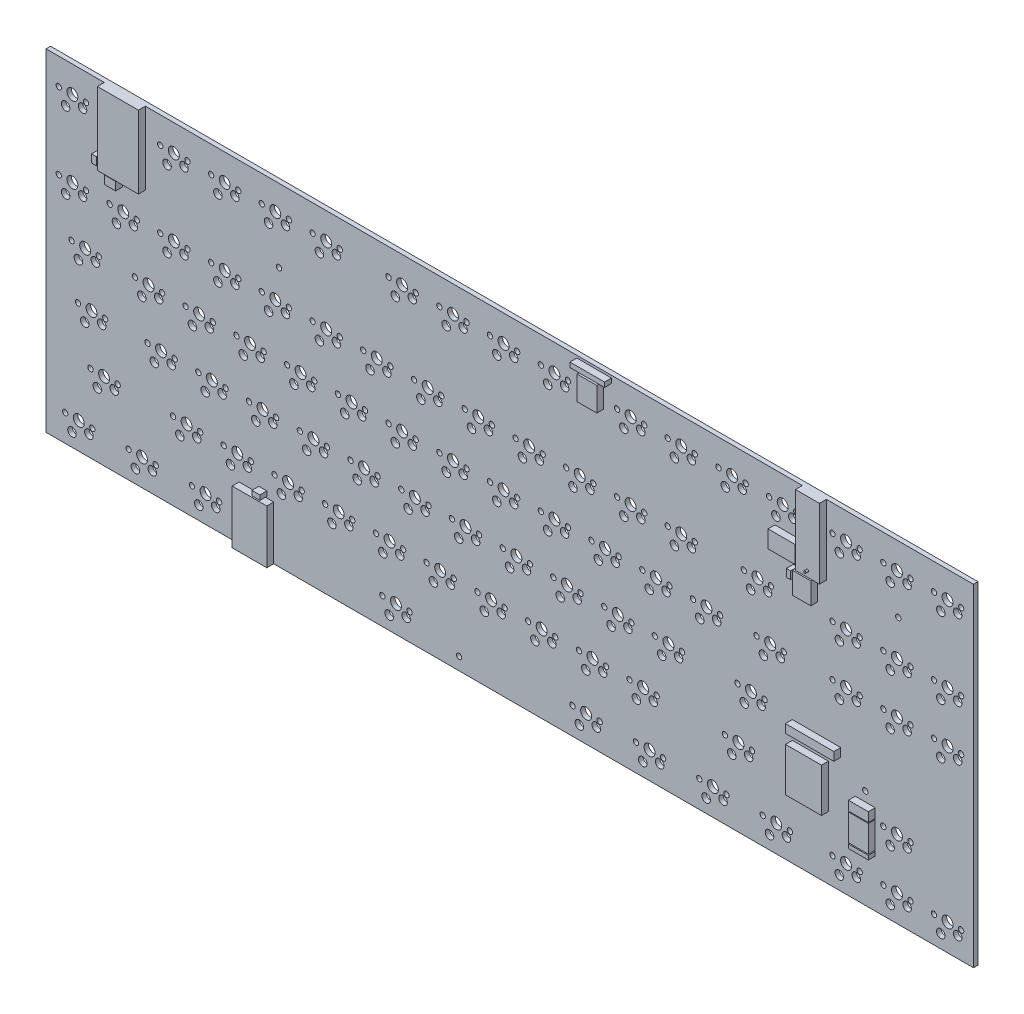
SolidWorks part; units mm, degrees
ref_plane "前视基准面" through (0, 0, 0) normal (0, 0, 1) x (1, 0, 0)
ref_plane "上视基准面" through (0, 0, 0) normal (0, 1, 0) x (1, 0, 0)
ref_plane "右视基准面" through (0, 0, 0) normal (1, 0, 0) x (0, 0, -1)
other "Configuration Table"
sketch "草图1" plane through (0, 0, 0) normal (0, 0, 1) x (1, 0, 0)
  line L9 (0, 0) -> (348.235, 0)
  line L10 (0, 0) -> (0, -124.714)
  line L16 (0, -124.714) -> (348.235, -124.714)
  line L17 (348.235, 0) -> (348.235, -124.714)
  dimension "D2" = 348.235
  dimension "D1" = 124.714
extrude "凸台-拉伸1" add sketch "草图1" along normal blind 1.7
sketch "草图3" plane through (0, 0, 1.7) normal (0, 0, 1) x (1, 0, 0)
  line L0 (0, 0) -> (0, -124.714) construction
  line L1 (348.235, 0) -> (0, 0) construction
  circle A0 centre (87.5, -27.4) radius 1
  circle A1 centre (155.1, -120) radius 1
  circle A2 centre (307.6, -87.5) radius 1
  circle A3 centre (320, -24.9) radius 1
  dimension "D1" = 2
  dimension "D2" = 87.5
  dimension "D3" = 27.4
  dimension "D4" = 155.1
  dimension "D5" = 120
  dimension "D6" = 307.6
  dimension "D7" = 87.5
  dimension "D8" = 320
  dimension "D9" = 24.9
extrude "切除-拉伸1" cut sketch "草图3" against normal through all
sketch "草图4" plane through (0, 0, 1.7) normal (0, 0, 1) x (1, 0, 0)
  line L0 (0, 0) -> (0, -124.714) construction
  line L1 (348.235, 0) -> (0, 0) construction
  circle A0 centre (9.9, -9.9) radius 2.05
  circle A1 centre (7.36, -14.91) radius 1.6
  circle A2 centre (13.71, -12.44) radius 1.6
  circle A3 centre (9.9, -38.5) radius 2.05
  circle A4 centre (7.36, -43.51) radius 1.6
  circle A5 centre (13.71, -41.04) radius 1.6
  circle A6 centre (14.7, -57.5) radius 2.05
  circle A7 centre (12.16, -62.51) radius 1.6
  circle A8 centre (18.51, -60.04) radius 1.6
  circle A9 centre (17.1, -76.6) radius 2.05
  circle A10 centre (14.56, -81.61) radius 1.6
  circle A11 centre (20.91, -79.14) radius 1.6
  circle A12 centre (21.8, -95.6) radius 2.05
  circle A13 centre (19.26, -100.61) radius 1.6
  circle A14 centre (25.61, -98.14) radius 1.6
  circle A15 centre (12.3, -114.7) radius 2.05
  circle A16 centre (9.76, -119.71) radius 1.6
  circle A17 centre (16.11, -117.24) radius 1.6
  circle A18 centre (48, -9.9) radius 2.05
  circle A19 centre (45.46, -14.91) radius 1.6
  circle A20 centre (51.81, -12.44) radius 1.6
  circle A21 centre (105.2, -9.9) radius 2.05
  circle A22 centre (102.66, -14.91) radius 1.6
  circle A23 centre (109.01, -12.44) radius 1.6
  circle A24 centre (133.7, -9.9) radius 2.05
  circle A25 centre (131.16, -14.91) radius 1.6
  circle A26 centre (137.51, -12.44) radius 1.6
  circle A27 centre (190.9, -9.9) radius 2.05
  circle A28 centre (188.36, -14.91) radius 1.6
  circle A29 centre (194.71, -12.44) radius 1.6
  circle A30 centre (219.5, -9.9) radius 2.05
  circle A31 centre (216.96, -14.91) radius 1.6
  circle A32 centre (223.31, -12.44) radius 1.6
  circle A33 centre (276.6, -9.9) radius 2.05
  circle A34 centre (274.06, -14.91) radius 1.6
  circle A35 centre (280.41, -12.44) radius 1.6
  circle A36 centre (300.4, -9.9) radius 2.05
  circle A37 centre (297.86, -14.91) radius 1.6
  circle A38 centre (304.21, -12.44) radius 1.6
  circle A39 centre (338.5, -9.9) radius 2.05
  circle A40 centre (335.96, -14.91) radius 1.6
  circle A41 centre (342.31, -12.44) radius 1.6
  circle A42 centre (260, -95.6) radius 2.05
  circle A43 centre (257.46, -100.61) radius 1.6
  circle A44 centre (263.81, -98.14) radius 1.6
  circle A45 centre (264.7, -76.6) radius 2.05
  circle A46 centre (262.16, -81.61) radius 1.6
  circle A47 centre (268.51, -79.14) radius 1.6
  circle A48 centre (271.9, -57.5) radius 2.05
  circle A49 centre (269.36, -62.51) radius 1.6
  circle A50 centre (275.71, -60.04) radius 1.6
  circle A51 centre (267.1, -38.5) radius 2.05
  circle A52 centre (264.56, -43.51) radius 1.6
  circle A53 centre (270.91, -41.04) radius 1.6
  circle A54 centre (274.2, -114.7) radius 2.05
  circle A55 centre (271.66, -119.71) radius 1.6
  circle A56 centre (278.01, -117.24) radius 1.6
  circle A57 centre (300.4, -38.5) radius 2.05
  circle A58 centre (297.86, -43.51) radius 1.6
  circle A59 centre (304.21, -41.04) radius 1.6
  circle A60 centre (338.5, -38.5) radius 2.05
  circle A61 centre (335.96, -43.51) radius 1.6
  circle A62 centre (342.31, -41.04) radius 1.6
  circle A63 centre (300.4, -57.5) radius 2.05
  circle A64 centre (297.86, -62.51) radius 1.6
  circle A65 centre (304.21, -60.04) radius 1.6
  circle A66 centre (338.5, -57.5) radius 2.05
  circle A67 centre (335.96, -62.51) radius 1.6
  circle A68 centre (342.31, -60.04) radius 1.6
  circle A69 centre (300.4, -114.7) radius 2.05
  circle A70 centre (297.86, -119.71) radius 1.6
  circle A71 centre (304.21, -117.24) radius 1.6
  circle A72 centre (319.5, -114.7) radius 2.05
  circle A73 centre (316.96, -119.71) radius 1.6
  circle A74 centre (323.31, -117.24) radius 1.6
  circle A75 centre (338.5, -114.7) radius 2.05
  circle A76 centre (335.96, -119.71) radius 1.6
  circle A77 centre (342.31, -117.24) radius 1.6
  circle A78 centre (319.5, -95.6) radius 2.05
  circle A79 centre (316.96, -100.61) radius 1.6
  circle A80 centre (323.31, -98.14) radius 1.6
  circle A81 centre (319.5, -57.5) radius 2.05
  circle A82 centre (316.96, -62.51) radius 1.6
  circle A83 centre (323.31, -60.04) radius 1.6
  circle A84 centre (319.5, -38.5) radius 2.05
  circle A85 centre (316.96, -43.51) radius 1.6
  circle A86 centre (323.31, -41.04) radius 1.6
  circle A87 centre (319.5, -9.9) radius 2.05
  circle A88 centre (316.96, -14.91) radius 1.6
  circle A89 centre (323.31, -12.44) radius 1.6
  circle A90 centre (131.4, -114.7) radius 2.05
  circle A91 centre (128.86, -119.71) radius 1.6
  circle A92 centre (135.21, -117.24) radius 1.6
  circle A93 centre (67.1, -9.9) radius 2.05
  circle A94 centre (64.56, -14.91) radius 1.6
  circle A95 centre (70.91, -12.44) radius 1.6
  circle A96 centre (86.1, -9.9) radius 2.05
  circle A97 centre (83.56, -14.91) radius 1.6
  circle A98 centre (89.91, -12.44) radius 1.6
  circle A99 centre (152.8, -9.9) radius 2.05
  circle A100 centre (150.26, -14.91) radius 1.6
  circle A101 centre (156.61, -12.44) radius 1.6
  circle A102 centre (171.8, -9.9) radius 2.05
  circle A103 centre (169.26, -14.91) radius 1.6
  circle A104 centre (175.61, -12.44) radius 1.6
  circle A105 centre (238.5, -9.9) radius 2.05
  circle A106 centre (235.96, -14.91) radius 1.6
  circle A107 centre (242.31, -12.44) radius 1.6
  circle A108 centre (257.6, -9.9) radius 2.05
  circle A109 centre (255.06, -14.91) radius 1.6
  circle A110 centre (261.41, -12.44) radius 1.6
  dimension "D1" = 4.1
  dimension "D8" = 3.2
  dimension "D9" = 3.2
  dimension "D10" = 4.1
  dimension "D15" = 3.2
  dimension "D16" = 3.2
  dimension "D19" = 4.1
  dimension "D24" = 3.2
  dimension "D25" = 3.2
  dimension "D28" = 4.1
  dimension "D33" = 3.2
  dimension "D34" = 3.2
  dimension "D37" = 4.1
  dimension "D42" = 3.2
  dimension "D43" = 3.2
  dimension "D46" = 4.1
  dimension "D51" = 3.2
  dimension "D52" = 3.2
  dimension "D55" = 4.1
  dimension "D60" = 3.2
  dimension "D61" = 3.2
  dimension "D63" = 4.1
  dimension "D68" = 3.2
  dimension "D69" = 3.2
  dimension "D75" = 3.2
  dimension "D76" = 3.2
  dimension "D78" = 4.1
  dimension "D83" = 3.2
  dimension "D84" = 3.2
  dimension "D85" = 4.1
  dimension "D91" = 3.2
  dimension "D92" = 3.2
  dimension "D93" = 4.1
  dimension "D98" = 3.2
  dimension "D99" = 3.2
  dimension "D100" = 4.1
  dimension "D105" = 3.2
  dimension "D106" = 3.2
  dimension "D107" = 4.1
  dimension "D112" = 3.2
  dimension "D113" = 3.2
  dimension "D114" = 4.1
  dimension "D123" = 3.2
  dimension "D124" = 4.1
  dimension "D126" = 3.2
  dimension "D131" = 3.2
  dimension "D132" = 4.1
  dimension "D133" = 3.2
  dimension "D138" = 3.2
  dimension "D139" = 4.1
  dimension "D140" = 3.2
  dimension "D145" = 3.2
  dimension "D146" = 4.1
  dimension "D147" = 3.2
  dimension "D152" = 3.2
  dimension "D153" = 4.1
  dimension "D154" = 3.2
  dimension "D163" = 3.2
  dimension "D164" = 4.1
  dimension "D165" = 3.2
  dimension "D170" = 3.2
  dimension "D171" = 4.1
  dimension "D172" = 3.2
  dimension "D177" = 3.2
  dimension "D178" = 4.1
  dimension "D179" = 3.2
  dimension "D184" = 3.2
  dimension "D185" = 4.1
  dimension "D186" = 3.2
  dimension "D191" = 3.2
  dimension "D192" = 4.1
  dimension "D193" = 3.2
  dimension "D198" = 3.2
  dimension "D199" = 4.1
  dimension "D200" = 3.2
  dimension "D205" = 3.2
  dimension "D206" = 4.1
  dimension "D207" = 3.2
  dimension "D212" = 3.2
  dimension "D213" = 4.1
  dimension "D214" = 3.2
  dimension "D219" = 3.2
  dimension "D220" = 4.1
  dimension "D221" = 3.2
  dimension "D226" = 3.2
  dimension "D227" = 4.1
  dimension "D228" = 3.2
  dimension "D233" = 3.2
  dimension "D234" = 4.1
  dimension "D235" = 3.2
  dimension "D241" = 3.2
  dimension "D242" = 4.1
  dimension "D243" = 3.2
  dimension "D245" = 4.1
  dimension "D250" = 3.2
  dimension "D251" = 3.2
  dimension "D252" = 4.1
  dimension "D257" = 3.2
  dimension "D258" = 3.2
  dimension "D259" = 4.1
  dimension "D264" = 3.2
  dimension "D265" = 3.2
  dimension "D266" = 4.1
  dimension "D271" = 3.2
  dimension "D272" = 3.2
  dimension "D273" = 4.1
  dimension "D278" = 3.2
  dimension "D279" = 3.2
  dimension "D280" = 4.1
  dimension "D285" = 3.2
  dimension "D286" = 3.2
  dimension "D2" = 9.9
  dimension "D3" = 9.9
  dimension "D4" = 5.01
  dimension "D5" = 2.54
  dimension "D6" = 3.81
  dimension "D7" = 2.54
  dimension "D11" = 5.01
  dimension "D12" = 2.54
  dimension "D13" = 3.81
  dimension "D14" = 2.54
  dimension "D17" = 9.9
  dimension "D18" = 38.5
  dimension "D20" = 5.01
  dimension "D21" = 2.54
  dimension "D22" = 3.81
  dimension "D23" = 2.54
  dimension "D26" = 14.7
  dimension "D27" = 57.5
  dimension "D29" = 5.01
  dimension "D30" = 2.54
  dimension "D31" = 3.81
  dimension "D32" = 2.54
  dimension "D35" = 17.1
  dimension "D36" = 76.6
  dimension "D38" = 5.01
  dimension "D39" = 2.54
  dimension "D40" = 3.81
  dimension "D41" = 2.54
  dimension "D44" = 21.8
  dimension "D45" = 95.6
  dimension "D47" = 5.01
  dimension "D48" = 2.54
  dimension "D49" = 3.81
  dimension "D50" = 2.54
  dimension "D53" = 12.3
  dimension "D54" = 114.7
  dimension "D56" = 5.01
  dimension "D57" = 2.54
  dimension "D58" = 3.81
  dimension "D59" = 2.54
  dimension "D62" = 48
  dimension "D64" = 5.01
  dimension "D65" = 2.54
  dimension "D66" = 3.81
  dimension "D67" = 2.54
  dimension "D70" = 105.2
  dimension "D71" = 5.01
  dimension "D72" = 2.54
  dimension "D73" = 3.81
  dimension "D74" = 2.54
  dimension "D77" = 133.7
  dimension "D79" = 5.01
  dimension "D80" = 2.54
  dimension "D81" = 3.81
  dimension "D82" = 2.54
  dimension "D86" = 190.9
  dimension "D87" = 5.01
  dimension "D88" = 2.54
  dimension "D89" = 3.81
  dimension "D90" = 2.54
  dimension "D94" = 5.01
  dimension "D95" = 2.54
  dimension "D96" = 3.81
  dimension "D97" = 2.54
  dimension "D101" = 5.01
  dimension "D102" = 2.54
  dimension "D103" = 3.81
  dimension "D104" = 2.54
  dimension "D108" = 5.01
  dimension "D109" = 2.54
  dimension "D110" = 3.81
  dimension "D111" = 2.54
  dimension "D115" = 219.5
  dimension "D116" = 276.6
  dimension "D117" = 300.4
  dimension "D118" = 338.5
  dimension "D119" = 5.01
  dimension "D120" = 2.54
  dimension "D121" = 3.81
  dimension "D122" = 2.54
  dimension "D125" = 260
  dimension "D127" = 5.01
  dimension "D128" = 2.54
  dimension "D129" = 3.81
  dimension "D130" = 2.54
  dimension "D134" = 5.01
  dimension "D135" = 2.54
  dimension "D136" = 3.81
  dimension "D137" = 2.54
  dimension "D141" = 5.01
  dimension "D142" = 2.54
  dimension "D143" = 3.81
  dimension "D144" = 2.54
  dimension "D148" = 5.01
  dimension "D149" = 2.54
  dimension "D150" = 3.81
  dimension "D151" = 2.54
  dimension "D155" = 264.7
  dimension "D156" = 271.9
  dimension "D157" = 267.1
  dimension "D158" = 274.2
  dimension "D159" = 5.01
  dimension "D160" = 2.54
  dimension "D161" = 3.81
  dimension "D162" = 2.54
  dimension "D166" = 5.01
  dimension "D167" = 2.54
  dimension "D168" = 3.81
  dimension "D169" = 2.54
  dimension "D173" = 5.01
  dimension "D174" = 2.54
  dimension "D175" = 3.81
  dimension "D176" = 2.54
  dimension "D180" = 5.01
  dimension "D181" = 2.54
  dimension "D182" = 3.81
  dimension "D183" = 2.54
  dimension "D187" = 5.01
  dimension "D188" = 2.54
  dimension "D189" = 3.81
  dimension "D190" = 2.54
  dimension "D194" = 5.01
  dimension "D195" = 2.54
  dimension "D196" = 3.81
  dimension "D197" = 2.54
  dimension "D201" = 5.01
  dimension "D202" = 2.54
  dimension "D203" = 3.81
  dimension "D204" = 2.54
  dimension "D208" = 5.01
  dimension "D209" = 2.54
  dimension "D210" = 3.81
  dimension "D211" = 2.54
  dimension "D215" = 5.01
  dimension "D216" = 2.54
  dimension "D217" = 3.81
  dimension "D218" = 2.54
  dimension "D222" = 5.01
  dimension "D223" = 2.54
  dimension "D224" = 3.81
  dimension "D225" = 2.54
  dimension "D229" = 5.01
  dimension "D230" = 2.54
  dimension "D231" = 3.81
  dimension "D232" = 2.54
  dimension "D236" = 319.5
  dimension "D237" = 5.01
  dimension "D238" = 2.54
  dimension "D239" = 3.81
  dimension "D240" = 2.54
  dimension "D244" = 131.4
  dimension "D246" = 5.01
  dimension "D247" = 2.54
  dimension "D248" = 3.81
  dimension "D249" = 2.54
  dimension "D253" = 5.01
  dimension "D254" = 2.54
  dimension "D255" = 3.81
  dimension "D256" = 2.54
  dimension "D260" = 5.01
  dimension "D261" = 2.54
  dimension "D262" = 3.81
  dimension "D263" = 2.54
  dimension "D267" = 5.01
  dimension "D268" = 2.54
  dimension "D269" = 3.81
  dimension "D270" = 2.54
  dimension "D274" = 5.01
  dimension "D275" = 2.54
  dimension "D276" = 3.81
  dimension "D277" = 2.54
  dimension "D281" = 5.01
  dimension "D282" = 2.54
  dimension "D283" = 3.81
  dimension "D284" = 2.54
  dimension "D287" = 67.1
  dimension "D288" = 86.1
  dimension "D289" = 152.8
  dimension "D290" = 171.8
  dimension "D291" = 238.5
  dimension "D292" = 257.6
extrude "切除-拉伸2" cut sketch "草图4" against normal through all
sketch "草图5" plane through (0, 0, 1.7) normal (0, 0, 1) x (1, 0, 0)
  line L0 (348.235, 0) -> (0, 0) construction
  line L1 (0, 0) -> (0, -124.714) construction
  line L2 (23.9, -38.5) -> (29, -38.5) construction
  line L3 (42.9, -38.5) -> (48, -38.5) construction
  line L4 (48, -38.5) -> (53.1, -38.5) construction
  line L5 (62, -38.5) -> (67.1, -38.5) construction
  line L6 (67.1, -38.5) -> (72.2, -38.5) construction
  line L7 (81, -38.5) -> (86.1, -38.5) construction
  line L8 (86.1, -38.5) -> (91.2, -38.5) construction
  line L9 (100.1, -38.5) -> (105.2, -38.5) construction
  line L10 (105.2, -38.5) -> (110.3, -38.5) construction
  line L11 (119.1, -38.5) -> (124.2, -38.5) construction
  line L12 (124.2, -38.5) -> (129.3, -38.5) construction
  line L13 (157.2, -38.5) -> (162.3, -38.5) construction
  line L14 (162.3, -38.5) -> (167.4, -38.5) construction
  line L15 (138.2, -38.5) -> (143.3, -38.5) construction
  line L16 (143.3, -38.5) -> (148.4, -38.5) construction
  line L17 (176.3, -38.5) -> (181.4, -38.5) construction
  line L18 (181.4, -38.5) -> (186.5, -38.5) construction
  line L19 (195.3, -38.5) -> (200.4, -38.5) construction
  line L20 (200.4, -38.5) -> (205.5, -38.5) construction
  line L21 (214.4, -38.5) -> (219.5, -38.5) construction
  line L22 (219.5, -38.5) -> (224.6, -38.5) construction
  line L23 (233.4, -38.5) -> (238.5, -38.5) construction
  line L24 (238.5, -38.5) -> (243.6, -38.5) construction
  line L25 (29, -38.5) -> (34.1, -38.5) construction
  circle A0 centre (29, -38.5) radius 2.05
  circle A1 centre (26.46, -43.51) radius 1.6
  circle A2 centre (32.81, -41.04) radius 1.6
  circle A3 centre (48, -38.5) radius 2.05
  circle A4 centre (45.46, -43.51) radius 1.6
  circle A5 centre (51.81, -41.04) radius 1.6
  circle A6 centre (67.1, -38.5) radius 2.05
  circle A7 centre (64.56, -43.51) radius 1.6
  circle A8 centre (70.91, -41.04) radius 1.6
  circle A9 centre (86.1, -38.5) radius 2.05
  circle A10 centre (83.56, -43.51) radius 1.6
  circle A11 centre (89.91, -41.04) radius 1.6
  circle A12 centre (105.2, -38.5) radius 2.05
  circle A13 centre (102.66, -43.51) radius 1.6
  circle A14 centre (109.01, -41.04) radius 1.6
  circle A15 centre (124.2, -38.5) radius 2.05
  circle A16 centre (121.66, -43.51) radius 1.6
  circle A17 centre (128.01, -41.04) radius 1.6
  circle A19 centre (143.3, -38.5) radius 2.05
  circle A20 centre (140.76, -43.51) radius 1.6
  circle A21 centre (147.11, -41.04) radius 1.6
  circle A22 centre (162.3, -38.5) radius 2.05
  circle A23 centre (159.76, -43.51) radius 1.6
  circle A24 centre (166.11, -41.04) radius 1.6
  circle A25 centre (181.4, -38.5) radius 2.05
  circle A26 centre (178.86, -43.51) radius 1.6
  circle A27 centre (185.21, -41.04) radius 1.6
  circle A28 centre (200.4, -38.5) radius 2.05
  circle A29 centre (197.86, -43.51) radius 1.6
  circle A30 centre (204.21, -41.04) radius 1.6
  circle A31 centre (219.5, -38.5) radius 2.05
  circle A32 centre (216.96, -43.51) radius 1.6
  circle A33 centre (223.31, -41.04) radius 1.6
  circle A34 centre (238.5, -38.5) radius 2.05
  circle A35 centre (235.96, -43.51) radius 1.6
  circle A36 centre (242.31, -41.04) radius 1.6
  circle A37 centre (23.9, -38.5) radius 1
  circle A38 centre (34.1, -38.5) radius 1
  circle A39 centre (42.9, -38.5) radius 1
  circle A40 centre (53.1, -38.5) radius 1
  circle A41 centre (62, -38.5) radius 1
  circle A42 centre (72.2, -38.5) radius 1
  circle A43 centre (81, -38.5) radius 1
  circle A44 centre (91.2, -38.5) radius 1
  circle A45 centre (100.1, -38.5) radius 1
  circle A46 centre (110.3, -38.5) radius 1
  circle A47 centre (119.1, -38.5) radius 1
  circle A48 centre (129.3, -38.5) radius 1
  circle A49 centre (138.2, -38.5) radius 1
  circle A50 centre (148.4, -38.5) radius 1
  circle A51 centre (157.2, -38.5) radius 1
  circle A52 centre (167.4, -38.5) radius 1
  circle A53 centre (176.3, -38.5) radius 1
  circle A54 centre (186.5, -38.5) radius 1
  circle A55 centre (195.3, -38.5) radius 1
  circle A56 centre (205.5, -38.5) radius 1
  circle A57 centre (214.4, -38.5) radius 1
  circle A58 centre (224.6, -38.5) radius 1
  circle A59 centre (233.4, -38.5) radius 1
  circle A60 centre (243.6, -38.5) radius 1
  dimension "D1" = 4.1
  dimension "D6" = 3.2
  dimension "D7" = 3.2
  dimension "D8" = 4.1
  dimension "D13" = 3.2
  dimension "D14" = 3.2
  dimension "D15" = 4.1
  dimension "D20" = 3.2
  dimension "D21" = 3.2
  dimension "D22" = 4.1
  dimension "D27" = 3.2
  dimension "D28" = 3.2
  dimension "D29" = 4.1
  dimension "D34" = 3.2
  dimension "D35" = 3.2
  dimension "D36" = 4.1
  dimension "D41" = 3.2
  dimension "D42" = 3.2
  dimension "D50" = 4.1
  dimension "D55" = 3.2
  dimension "D56" = 3.2
  dimension "D57" = 4.1
  dimension "D62" = 3.2
  dimension "D63" = 3.2
  dimension "D64" = 4.1
  dimension "D69" = 3.2
  dimension "D70" = 3.2
  dimension "D71" = 4.1
  dimension "D76" = 3.2
  dimension "D77" = 3.2
  dimension "D78" = 4.1
  dimension "D83" = 3.2
  dimension "D84" = 3.2
  dimension "D85" = 4.1
  dimension "D90" = 3.2
  dimension "D91" = 3.2
  dimension "D98" = 2
  dimension "D2" = 5.01
  dimension "D3" = 2.54
  dimension "D4" = 3.81
  dimension "D5" = 2.54
  dimension "D9" = 5.01
  dimension "D10" = 2.54
  dimension "D11" = 3.81
  dimension "D12" = 2.54
  dimension "D16" = 5.01
  dimension "D17" = 2.54
  dimension "D18" = 3.81
  dimension "D19" = 2.54
  dimension "D23" = 5.01
  dimension "D24" = 2.54
  dimension "D25" = 3.81
  dimension "D26" = 2.54
  dimension "D30" = 5.01
  dimension "D31" = 2.54
  dimension "D32" = 3.81
  dimension "D33" = 2.54
  dimension "D37" = 5.01
  dimension "D38" = 2.54
  dimension "D39" = 3.81
  dimension "D40" = 2.54
  dimension "D43" = 38.5
  dimension "D44" = 29
  dimension "D45" = 48
  dimension "D46" = 67.1
  dimension "D47" = 86.1
  dimension "D48" = 105.2
  dimension "D49" = 124.2
  dimension "D51" = 5.01
  dimension "D52" = 2.54
  dimension "D53" = 3.81
  dimension "D54" = 2.54
  dimension "D58" = 5.01
  dimension "D59" = 2.54
  dimension "D60" = 3.81
  dimension "D61" = 2.54
  dimension "D65" = 5.01
  dimension "D66" = 2.54
  dimension "D67" = 3.81
  dimension "D68" = 2.54
  dimension "D72" = 5.01
  dimension "D73" = 2.54
  dimension "D74" = 3.81
  dimension "D75" = 2.54
  dimension "D79" = 5.01
  dimension "D80" = 2.54
  dimension "D81" = 3.81
  dimension "D82" = 2.54
  dimension "D86" = 5.01
  dimension "D87" = 2.54
  dimension "D88" = 3.81
  dimension "D89" = 2.54
  dimension "D92" = 143.3
  dimension "D93" = 162.3
  dimension "D94" = 181.4
  dimension "D95" = 200.4
  dimension "D96" = 219.5
  dimension "D97" = 238.5
  dimension "D99" = 5.1
extrude "切除-拉伸3" cut sketch "草图5" against normal through all
sketch "草图6" plane through (0, 0, 1.7) normal (0, 0, 1) x (1, 0, 0)
  line L0 (348.235, 0) -> (0, 0) construction
  line L1 (0, 0) -> (0, -124.714) construction
  circle A0 centre (38.5, -57.5) radius 2.05
  circle A1 centre (35.96, -62.51) radius 1.6
  circle A2 centre (42.31, -60.04) radius 1.6
  circle A34 centre (33.4, -57.5) radius 1
  circle A35 centre (43.6, -57.5) radius 1
  circle A36 centre (57.5, -57.5) radius 2.05
  circle A37 centre (54.96, -62.51) radius 1.6
  circle A38 centre (61.31, -60.04) radius 1.6
  circle A39 centre (52.4, -57.5) radius 1
  circle A40 centre (62.6, -57.5) radius 1
  circle A41 centre (76.6, -57.5) radius 2.05
  circle A42 centre (74.06, -62.51) radius 1.6
  circle A43 centre (80.41, -60.04) radius 1.6
  circle A44 centre (71.5, -57.5) radius 1
  circle A45 centre (81.7, -57.5) radius 1
  circle A46 centre (95.6, -57.5) radius 2.05
  circle A47 centre (93.06, -62.51) radius 1.6
  circle A48 centre (99.41, -60.04) radius 1.6
  circle A49 centre (90.5, -57.5) radius 1
  circle A50 centre (100.7, -57.5) radius 1
  circle A51 centre (114.7, -57.5) radius 2.05
  circle A52 centre (112.16, -62.51) radius 1.6
  circle A53 centre (118.51, -60.04) radius 1.6
  circle A54 centre (109.6, -57.5) radius 1
  circle A55 centre (119.8, -57.5) radius 1
  circle A56 centre (133.7, -57.5) radius 2.05
  circle A57 centre (131.16, -62.51) radius 1.6
  circle A58 centre (137.51, -60.04) radius 1.6
  circle A59 centre (128.6, -57.5) radius 1
  circle A60 centre (138.8, -57.5) radius 1
  circle A61 centre (152.8, -57.5) radius 2.05
  circle A62 centre (150.26, -62.51) radius 1.6
  circle A63 centre (156.61, -60.04) radius 1.6
  circle A64 centre (147.7, -57.5) radius 1
  circle A65 centre (157.9, -57.5) radius 1
  circle A66 centre (171.8, -57.5) radius 2.05
  circle A67 centre (169.26, -62.51) radius 1.6
  circle A68 centre (175.61, -60.04) radius 1.6
  circle A69 centre (166.7, -57.5) radius 1
  circle A70 centre (176.9, -57.5) radius 1
  circle A71 centre (190.9, -57.5) radius 2.05
  circle A72 centre (188.36, -62.51) radius 1.6
  circle A73 centre (194.71, -60.04) radius 1.6
  circle A74 centre (185.8, -57.5) radius 1
  circle A75 centre (196, -57.5) radius 1
  circle A76 centre (209.9, -57.5) radius 2.05
  circle A77 centre (207.36, -62.51) radius 1.6
  circle A78 centre (213.71, -60.04) radius 1.6
  circle A79 centre (204.8, -57.5) radius 1
  circle A80 centre (215, -57.5) radius 1
  circle A81 centre (229, -57.5) radius 2.05
  circle A82 centre (226.46, -62.51) radius 1.6
  circle A83 centre (232.81, -60.04) radius 1.6
  circle A84 centre (223.9, -57.5) radius 1
  circle A85 centre (234.1, -57.5) radius 1
  circle A86 centre (248, -57.5) radius 2.05
  circle A87 centre (245.46, -62.51) radius 1.6
  circle A88 centre (251.81, -60.04) radius 1.6
  circle A89 centre (242.9, -57.5) radius 1
  circle A90 centre (253.1, -57.5) radius 1
  dimension "D1" = 4.1
  dimension "D6" = 3.2
  dimension "D7" = 3.2
  dimension "D8" = 5.1
  dimension "D13" = 2.54
  dimension "D14" = 3.81
  dimension "D15" = 2.54
  dimension "D20" = 2
  dimension "D21" = 4.1
  dimension "D22" = 5.01
  dimension "D27" = 3.2
  dimension "D28" = 5.1
  dimension "D29" = 5.1
  dimension "D34" = 3.81
  dimension "D35" = 2.54
  dimension "D36" = 3.2
  dimension "D41" = 4.1
  dimension "D42" = 5.01
  dimension "D43" = 2.54
  dimension "D48" = 5.1
  dimension "D49" = 5.1
  dimension "D50" = 2
  dimension "D55" = 2.54
  dimension "D56" = 3.2
  dimension "D57" = 3.2
  dimension "D62" = 5.01
  dimension "D63" = 2.54
  dimension "D64" = 3.81
  dimension "D69" = 5.1
  dimension "D70" = 2
  dimension "D71" = 4.1
  dimension "D76" = 3.2
  dimension "D77" = 3.2
  dimension "D10" = 2
  dimension "D11" = 4.1
  dimension "D16" = 3.2
  dimension "D17" = 3.2
  dimension "D26" = 3.2
  dimension "D30" = 2
  dimension "D31" = 4.1
  dimension "D37" = 3.2
  dimension "D40" = 2
  dimension "D46" = 3.2
  dimension "D47" = 3.2
  dimension "D51" = 4.1
  dimension "D60" = 2
  dimension "D61" = 4.1
  dimension "D66" = 3.2
  dimension "D67" = 3.2
  dimension "D81" = 2
  dimension "D82" = 4.1
  dimension "D87" = 3.2
  dimension "D88" = 3.2
  dimension "D91" = 2
  dimension "D92" = 4.1
  dimension "D97" = 3.2
  dimension "D98" = 3.2
  dimension "D101" = 2
  dimension "D102" = 4.1
  dimension "D107" = 3.2
  dimension "D108" = 3.2
  dimension "D111" = 2
  dimension "D123" = 4.1
  dimension "D128" = 3.2
  dimension "D129" = 3.2
  dimension "D132" = 2
  dimension "D2" = 5.01
  dimension "D3" = 2.54
  dimension "D4" = 3.81
  dimension "D5" = 2.54
  dimension "D9" = 5.1
  dimension "D12" = 5.01
  dimension "D18" = 5.1
  dimension "D19" = 5.1
  dimension "D23" = 2.54
  dimension "D24" = 3.81
  dimension "D25" = 2.54
  dimension "D32" = 5.01
  dimension "D33" = 2.54
  dimension "D38" = 5.1
  dimension "D39" = 5.1
  dimension "D44" = 3.81
  dimension "D45" = 2.54
  dimension "D52" = 5.01
  dimension "D53" = 2.54
  dimension "D54" = 3.81
  dimension "D58" = 5.1
  dimension "D59" = 5.1
  dimension "D65" = 2.54
  dimension "D68" = 5.1
  dimension "D72" = 5.01
  dimension "D73" = 2.54
  dimension "D74" = 3.81
  dimension "D75" = 2.54
  dimension "D78" = 57.5
  dimension "D79" = 5.1
  dimension "D80" = 5.1
  dimension "D83" = 5.01
  dimension "D84" = 2.54
  dimension "D85" = 3.81
  dimension "D86" = 2.54
  dimension "D89" = 5.1
  dimension "D90" = 5.1
  dimension "D93" = 5.01
  dimension "D94" = 2.54
  dimension "D95" = 3.81
  dimension "D96" = 2.54
  dimension "D99" = 5.1
  dimension "D100" = 5.1
  dimension "D103" = 5.01
  dimension "D104" = 2.54
  dimension "D105" = 3.81
  dimension "D106" = 2.54
  dimension "D109" = 5.1
  dimension "D110" = 5.1
  dimension "D112" = 38.5
  dimension "D113" = 57.5
  dimension "D114" = 76.6
  dimension "D115" = 95.6
  dimension "D116" = 114.7
  dimension "D117" = 133.7
  dimension "D118" = 152.8
  dimension "D119" = 171.8
  dimension "D120" = 190.9
  dimension "D121" = 209.9
  dimension "D122" = 229
  dimension "D124" = 5.01
  dimension "D125" = 2.54
  dimension "D126" = 3.81
  dimension "D127" = 2.54
  dimension "D130" = 5.1
  dimension "D131" = 5.1
  dimension "D133" = 248
extrude "切除-拉伸4" cut sketch "草图6" against normal through all
sketch "草图8" plane through (0, 0, 1.7) normal (0, 0, 1) x (1, 0, 0)
  line L0 (348.235, 0) -> (0, 0) construction
  line L1 (0, 0) -> (0, -124.714) construction
  circle A0 centre (43.2, -76.6) radius 2.05
  circle A1 centre (40.66, -81.61) radius 1.6
  circle A2 centre (47.01, -79.14) radius 1.6
  circle A3 centre (38.1, -76.6) radius 1
  circle A4 centre (48.3, -76.6) radius 1
  circle A5 centre (62.3, -76.6) radius 2.05
  circle A6 centre (59.76, -81.61) radius 1.6
  circle A7 centre (66.11, -79.14) radius 1.6
  circle A8 centre (57.2, -76.6) radius 1
  circle A9 centre (67.4, -76.6) radius 1
  circle A10 centre (81.3, -76.6) radius 2.05
  circle A11 centre (78.76, -81.61) radius 1.6
  circle A12 centre (85.11, -79.14) radius 1.6
  circle A13 centre (76.2, -76.6) radius 1
  circle A14 centre (86.4, -76.6) radius 1
  circle A15 centre (100.4, -76.6) radius 2.05
  circle A16 centre (97.86, -81.61) radius 1.6
  circle A17 centre (104.21, -79.14) radius 1.6
  circle A18 centre (95.3, -76.6) radius 1
  circle A19 centre (105.5, -76.6) radius 1
  circle A20 centre (119.4, -76.6) radius 2.05
  circle A21 centre (116.86, -81.61) radius 1.6
  circle A22 centre (123.21, -79.14) radius 1.6
  circle A23 centre (114.3, -76.6) radius 1
  circle A24 centre (124.5, -76.6) radius 1
  circle A25 centre (138.5, -76.6) radius 2.05
  circle A26 centre (135.96, -81.61) radius 1.6
  circle A27 centre (142.31, -79.14) radius 1.6
  circle A28 centre (133.4, -76.6) radius 1
  circle A29 centre (143.6, -76.6) radius 1
  circle A30 centre (157.5, -76.6) radius 2.05
  circle A31 centre (154.96, -81.61) radius 1.6
  circle A32 centre (161.31, -79.14) radius 1.6
  circle A33 centre (152.4, -76.6) radius 1
  circle A34 centre (162.6, -76.6) radius 1
  circle A35 centre (176.6, -76.6) radius 2.05
  circle A36 centre (174.06, -81.61) radius 1.6
  circle A37 centre (180.41, -79.14) radius 1.6
  circle A38 centre (171.5, -76.6) radius 1
  circle A39 centre (181.7, -76.6) radius 1
  circle A40 centre (195.6, -76.6) radius 2.05
  circle A41 centre (193.06, -81.61) radius 1.6
  circle A42 centre (199.41, -79.14) radius 1.6
  circle A43 centre (190.5, -76.6) radius 1
  circle A44 centre (200.7, -76.6) radius 1
  circle A45 centre (214.7, -76.6) radius 2.05
  circle A46 centre (212.16, -81.61) radius 1.6
  circle A47 centre (218.51, -79.14) radius 1.6
  circle A48 centre (209.6, -76.6) radius 1
  circle A49 centre (219.8, -76.6) radius 1
  circle A50 centre (233.7, -76.6) radius 2.05
  circle A51 centre (231.16, -81.61) radius 1.6
  circle A52 centre (237.51, -79.14) radius 1.6
  circle A53 centre (228.6, -76.6) radius 1
  circle A54 centre (238.8, -76.6) radius 1
  dimension "D1" = 4.1
  dimension "D6" = 3.2
  dimension "D7" = 3.2
  dimension "D10" = 2
  dimension "D11" = 4.1
  dimension "D16" = 3.2
  dimension "D17" = 3.2
  dimension "D20" = 2
  dimension "D21" = 4.1
  dimension "D26" = 3.2
  dimension "D27" = 3.2
  dimension "D30" = 2
  dimension "D31" = 4.1
  dimension "D36" = 3.2
  dimension "D37" = 3.2
  dimension "D40" = 2
  dimension "D41" = 4.1
  dimension "D46" = 3.2
  dimension "D47" = 3.2
  dimension "D50" = 2
  dimension "D51" = 4.1
  dimension "D56" = 3.2
  dimension "D57" = 3.2
  dimension "D60" = 2
  dimension "D61" = 4.1
  dimension "D66" = 3.2
  dimension "D67" = 3.2
  dimension "D70" = 2
  dimension "D71" = 4.1
  dimension "D76" = 3.2
  dimension "D77" = 3.2
  dimension "D80" = 2
  dimension "D81" = 4.1
  dimension "D86" = 3.2
  dimension "D87" = 3.2
  dimension "D90" = 2
  dimension "D91" = 4.1
  dimension "D96" = 3.2
  dimension "D97" = 3.2
  dimension "D100" = 2
  dimension "D101" = 4.1
  dimension "D106" = 3.2
  dimension "D107" = 3.2
  dimension "D110" = 2
  dimension "D2" = 5.01
  dimension "D3" = 2.54
  dimension "D4" = 3.81
  dimension "D5" = 2.54
  dimension "D8" = 5.1
  dimension "D9" = 5.1
  dimension "D12" = 5.01
  dimension "D13" = 2.54
  dimension "D14" = 3.81
  dimension "D15" = 2.54
  dimension "D18" = 5.1
  dimension "D19" = 5.1
  dimension "D22" = 5.01
  dimension "D23" = 2.54
  dimension "D24" = 3.81
  dimension "D25" = 2.54
  dimension "D28" = 5.1
  dimension "D29" = 5.1
  dimension "D32" = 5.01
  dimension "D33" = 2.54
  dimension "D34" = 3.81
  dimension "D35" = 2.54
  dimension "D38" = 5.1
  dimension "D39" = 5.1
  dimension "D42" = 5.01
  dimension "D43" = 2.54
  dimension "D44" = 3.81
  dimension "D45" = 2.54
  dimension "D48" = 5.1
  dimension "D49" = 5.1
  dimension "D52" = 5.01
  dimension "D53" = 2.54
  dimension "D54" = 3.81
  dimension "D55" = 2.54
  dimension "D58" = 5.1
  dimension "D59" = 5.1
  dimension "D62" = 5.01
  dimension "D63" = 2.54
  dimension "D64" = 3.81
  dimension "D65" = 2.54
  dimension "D68" = 5.1
  dimension "D69" = 5.1
  dimension "D72" = 5.01
  dimension "D73" = 2.54
  dimension "D74" = 3.81
  dimension "D75" = 2.54
  dimension "D78" = 5.1
  dimension "D79" = 5.1
  dimension "D82" = 5.01
  dimension "D83" = 2.54
  dimension "D84" = 3.81
  dimension "D85" = 2.54
  dimension "D88" = 5.1
  dimension "D89" = 5.1
  dimension "D92" = 5.01
  dimension "D93" = 2.54
  dimension "D94" = 3.81
  dimension "D95" = 2.54
  dimension "D98" = 5.1
  dimension "D99" = 5.1
  dimension "D102" = 5.01
  dimension "D103" = 2.54
  dimension "D104" = 3.81
  dimension "D105" = 2.54
  dimension "D108" = 5.1
  dimension "D109" = 5.1
  dimension "D111" = 76.6
  dimension "D112" = 43.2
  dimension "D113" = 62.3
  dimension "D114" = 81.3
  dimension "D115" = 100.4
  dimension "D116" = 119.4
  dimension "D117" = 138.5
  dimension "D118" = 157.5
  dimension "D119" = 176.6
  dimension "D120" = 195.6
  dimension "D121" = 214.7
  dimension "D122" = 233.7
extrude "切除-拉伸5" cut sketch "草图8" against normal through all
sketch "草图10" plane through (0, 0, 1.7) normal (0, 0, 1) x (1, 0, 0)
  line L0 (348.235, 0) -> (0, 0) construction
  line L1 (0, 0) -> (0, -124.714) construction
  circle A0 centre (52.8, -95.6) radius 2.05
  circle A1 centre (50.26, -100.61) radius 1.6
  circle A2 centre (56.61, -98.14) radius 1.6
  circle A3 centre (47.7, -95.6) radius 1
  circle A4 centre (57.9, -95.6) radius 1
  circle A5 centre (71.8, -95.6) radius 2.05
  circle A6 centre (69.26, -100.61) radius 1.6
  circle A7 centre (75.61, -98.14) radius 1.6
  circle A8 centre (66.7, -95.6) radius 1
  circle A9 centre (76.9, -95.6) radius 1
  circle A10 centre (90.9, -95.6) radius 2.05
  circle A11 centre (88.36, -100.61) radius 1.6
  circle A12 centre (94.71, -98.14) radius 1.6
  circle A13 centre (85.8, -95.6) radius 1
  circle A14 centre (96, -95.6) radius 1
  circle A15 centre (109.9, -95.6) radius 2.05
  circle A16 centre (107.36, -100.61) radius 1.6
  circle A17 centre (113.71, -98.14) radius 1.6
  circle A18 centre (104.8, -95.6) radius 1
  circle A19 centre (115, -95.6) radius 1
  circle A20 centre (129, -95.6) radius 2.05
  circle A21 centre (126.46, -100.61) radius 1.6
  circle A22 centre (132.81, -98.14) radius 1.6
  circle A23 centre (123.9, -95.6) radius 1
  circle A24 centre (134.1, -95.6) radius 1
  circle A25 centre (148, -95.6) radius 2.05
  circle A26 centre (145.46, -100.61) radius 1.6
  circle A27 centre (151.81, -98.14) radius 1.6
  circle A28 centre (142.9, -95.6) radius 1
  circle A29 centre (153.1, -95.6) radius 1
  circle A30 centre (167.1, -95.6) radius 2.05
  circle A31 centre (164.56, -100.61) radius 1.6
  circle A32 centre (170.91, -98.14) radius 1.6
  circle A33 centre (162, -95.6) radius 1
  circle A34 centre (172.2, -95.6) radius 1
  circle A35 centre (186.1, -95.6) radius 2.05
  circle A36 centre (183.56, -100.61) radius 1.6
  circle A37 centre (189.91, -98.14) radius 1.6
  circle A38 centre (181, -95.6) radius 1
  circle A39 centre (191.2, -95.6) radius 1
  circle A40 centre (205.2, -95.6) radius 2.05
  circle A41 centre (202.66, -100.61) radius 1.6
  circle A42 centre (209.01, -98.14) radius 1.6
  circle A43 centre (200.1, -95.6) radius 1
  circle A44 centre (210.3, -95.6) radius 1
  circle A45 centre (224.2, -95.6) radius 2.05
  circle A46 centre (221.66, -100.61) radius 1.6
  circle A47 centre (228.01, -98.14) radius 1.6
  circle A48 centre (219.1, -95.6) radius 1
  circle A49 centre (229.3, -95.6) radius 1
  circle A51 centre (36.1, -114.7) radius 2.05
  circle A52 centre (33.56, -119.71) radius 1.6
  circle A53 centre (39.91, -117.24) radius 1.6
  circle A54 centre (31, -114.7) radius 1
  circle A55 centre (41.2, -114.7) radius 1
  circle A56 centre (59.9, -114.7) radius 2.05
  circle A57 centre (57.36, -119.71) radius 1.6
  circle A58 centre (63.71, -117.24) radius 1.6
  circle A59 centre (54.8, -114.7) radius 1
  circle A60 centre (65, -114.7) radius 1
  circle A61 centre (202.8, -114.7) radius 2.05
  circle A62 centre (200.26, -119.71) radius 1.6
  circle A63 centre (206.61, -117.24) radius 1.6
  circle A64 centre (197.7, -114.7) radius 1
  circle A65 centre (207.9, -114.7) radius 1
  circle A66 centre (226.6, -114.7) radius 2.05
  circle A67 centre (224.06, -119.71) radius 1.6
  circle A68 centre (230.41, -117.24) radius 1.6
  circle A69 centre (221.5, -114.7) radius 1
  circle A70 centre (231.7, -114.7) radius 1
  circle A71 centre (250.4, -114.7) radius 2.05
  circle A72 centre (247.86, -119.71) radius 1.6
  circle A73 centre (254.21, -117.24) radius 1.6
  circle A74 centre (245.3, -114.7) radius 1
  circle A75 centre (255.5, -114.7) radius 1
  dimension "D1" = 4.1
  dimension "D6" = 3.2
  dimension "D7" = 3.2
  dimension "D10" = 2
  dimension "D11" = 4.1
  dimension "D16" = 3.2
  dimension "D17" = 3.2
  dimension "D20" = 2
  dimension "D21" = 4.1
  dimension "D26" = 3.2
  dimension "D27" = 3.2
  dimension "D30" = 2
  dimension "D31" = 4.1
  dimension "D36" = 3.2
  dimension "D37" = 3.2
  dimension "D40" = 2
  dimension "D41" = 4.1
  dimension "D46" = 3.2
  dimension "D47" = 3.2
  dimension "D50" = 2
  dimension "D51" = 4.1
  dimension "D56" = 3.2
  dimension "D57" = 3.2
  dimension "D60" = 2
  dimension "D61" = 4.1
  dimension "D66" = 3.2
  dimension "D67" = 3.2
  dimension "D70" = 2
  dimension "D71" = 4.1
  dimension "D76" = 3.2
  dimension "D77" = 3.2
  dimension "D80" = 2
  dimension "D81" = 4.1
  dimension "D86" = 3.2
  dimension "D87" = 3.2
  dimension "D90" = 2
  dimension "D91" = 4.1
  dimension "D96" = 3.2
  dimension "D97" = 3.2
  dimension "D100" = 2
  dimension "D112" = 4.1
  dimension "D117" = 3.2
  dimension "D118" = 3.2
  dimension "D121" = 2
  dimension "D122" = 4.1
  dimension "D127" = 3.2
  dimension "D128" = 3.2
  dimension "D131" = 2
  dimension "D132" = 4.1
  dimension "D137" = 3.2
  dimension "D138" = 3.2
  dimension "D141" = 2
  dimension "D142" = 4.1
  dimension "D147" = 3.2
  dimension "D148" = 3.2
  dimension "D151" = 2
  dimension "D152" = 4.1
  dimension "D157" = 3.2
  dimension "D158" = 3.2
  dimension "D161" = 2
  dimension "D2" = 5.01
  dimension "D3" = 2.54
  dimension "D4" = 3.81
  dimension "D5" = 2.54
  dimension "D8" = 5.1
  dimension "D9" = 5.1
  dimension "D12" = 5.01
  dimension "D13" = 2.54
  dimension "D14" = 3.81
  dimension "D15" = 2.54
  dimension "D18" = 5.1
  dimension "D19" = 5.1
  dimension "D22" = 5.01
  dimension "D23" = 2.54
  dimension "D24" = 3.81
  dimension "D25" = 2.54
  dimension "D28" = 5.1
  dimension "D29" = 5.1
  dimension "D32" = 5.01
  dimension "D33" = 2.54
  dimension "D34" = 3.81
  dimension "D35" = 2.54
  dimension "D38" = 5.1
  dimension "D39" = 5.1
  dimension "D42" = 5.01
  dimension "D43" = 2.54
  dimension "D44" = 3.81
  dimension "D45" = 2.54
  dimension "D48" = 5.1
  dimension "D49" = 5.1
  dimension "D52" = 5.01
  dimension "D53" = 2.54
  dimension "D54" = 3.81
  dimension "D55" = 2.54
  dimension "D58" = 5.1
  dimension "D59" = 5.1
  dimension "D62" = 5.01
  dimension "D63" = 2.54
  dimension "D64" = 3.81
  dimension "D65" = 2.54
  dimension "D68" = 5.1
  dimension "D69" = 5.1
  dimension "D72" = 5.01
  dimension "D73" = 2.54
  dimension "D74" = 3.81
  dimension "D75" = 2.54
  dimension "D78" = 5.1
  dimension "D79" = 5.1
  dimension "D82" = 5.01
  dimension "D83" = 2.54
  dimension "D84" = 3.81
  dimension "D85" = 2.54
  dimension "D88" = 5.1
  dimension "D89" = 5.1
  dimension "D92" = 5.01
  dimension "D93" = 2.54
  dimension "D94" = 3.81
  dimension "D95" = 2.54
  dimension "D98" = 5.1
  dimension "D99" = 5.1
  dimension "D101" = 95.6
  dimension "D102" = 52.8
  dimension "D103" = 71.8
  dimension "D104" = 90.9
  dimension "D105" = 109.9
  dimension "D106" = 129
  dimension "D107" = 148
  dimension "D108" = 167.1
  dimension "D109" = 186.1
  dimension "D110" = 205.2
  dimension "D111" = 224.2
  dimension "D113" = 5.01
  dimension "D114" = 2.54
  dimension "D115" = 3.81
  dimension "D116" = 2.54
  dimension "D119" = 5.1
  dimension "D120" = 5.1
  dimension "D123" = 5.01
  dimension "D124" = 2.54
  dimension "D125" = 3.81
  dimension "D126" = 2.54
  dimension "D129" = 5.1
  dimension "D130" = 5.1
  dimension "D133" = 5.01
  dimension "D134" = 2.54
  dimension "D135" = 3.81
  dimension "D136" = 2.54
  dimension "D139" = 5.1
  dimension "D140" = 5.1
  dimension "D143" = 5.01
  dimension "D144" = 2.54
  dimension "D145" = 3.81
  dimension "D146" = 2.54
  dimension "D149" = 5.1
  dimension "D150" = 5.1
  dimension "D153" = 5.01
  dimension "D154" = 2.54
  dimension "D155" = 3.81
  dimension "D156" = 2.54
  dimension "D159" = 5.1
  dimension "D160" = 5.1
  dimension "D162" = 114.7
  dimension "D163" = 36.1
  dimension "D164" = 59.9
  dimension "D165" = 202.8
  dimension "D166" = 226.6
  dimension "D167" = 250.4
extrude "切除-拉伸6" cut sketch "草图10" against normal through all
sketch "草图11" plane through (0, 0, 1.7) normal (0, 0, 1) x (1, 0, 0)
  line L0 (4.8, -9.9) -> (9.9, -9.9) construction
  line L1 (9.9, -9.9) -> (15, -9.9) construction
  line L2 (48, -9.9) -> (42.9, -9.9) construction
  line L3 (48, -9.9) -> (53.1, -9.9) construction
  line L4 (62, -9.9) -> (67.1, -9.9) construction
  line L5 (67.1, -9.9) -> (72.2, -9.9) construction
  line L6 (81, -9.9) -> (86.1, -9.9) construction
  line L7 (86.1, -9.9) -> (91.2, -9.9) construction
  line L8 (100.1, -9.9) -> (105.2, -9.9) construction
  line L9 (105.2, -9.9) -> (110.3, -9.9) construction
  line L10 (128.6, -9.9) -> (133.7, -9.9) construction
  line L11 (133.7, -9.9) -> (138.8, -9.9) construction
  line L12 (147.7, -9.9) -> (152.8, -9.9) construction
  line L13 (152.8, -9.9) -> (157.9, -9.9) construction
  line L14 (166.7, -9.9) -> (171.8, -9.9) construction
  line L15 (171.8, -9.9) -> (176.9, -9.9) construction
  line L16 (185.8, -9.9) -> (190.9, -9.9) construction
  line L17 (190.9, -9.9) -> (196, -9.9) construction
  line L18 (214.4, -9.9) -> (219.5, -9.9) construction
  line L19 (219.5, -9.9) -> (224.6, -9.9) construction
  line L20 (233.4, -9.9) -> (238.5, -9.9) construction
  line L21 (238.5, -9.9) -> (243.6, -9.9) construction
  line L22 (252.5, -9.9) -> (257.6, -9.9) construction
  line L23 (257.6, -9.9) -> (262.7, -9.9) construction
  line L24 (271.5, -9.9) -> (276.6, -9.9) construction
  line L25 (276.6, -9.9) -> (281.7, -9.9) construction
  line L26 (295.3, -9.9) -> (300.4, -9.9) construction
  line L27 (300.4, -9.9) -> (305.5, -9.9) construction
  line L28 (314.4, -9.9) -> (319.5, -9.9) construction
  line L29 (319.5, -9.9) -> (324.6, -9.9) construction
  line L32 (333.4, -9.9) -> (338.5, -9.9) construction
  line L33 (338.5, -9.9) -> (343.6, -9.9) construction
  line L34 (262, -38.5) -> (267.1, -38.5) construction
  line L35 (267.1, -38.5) -> (272.2, -38.5) construction
  line L36 (295.3, -38.5) -> (300.4, -38.5) construction
  line L37 (300.4, -38.5) -> (305.5, -38.5) construction
  line L38 (314.4, -38.5) -> (319.5, -38.5) construction
  line L39 (319.5, -38.5) -> (324.6, -38.5) construction
  line L40 (333.4, -38.5) -> (338.5, -38.5) construction
  line L41 (338.5, -38.5) -> (343.6, -38.5) construction
  line L42 (266.8, -57.5) -> (271.9, -57.5) construction
  line L43 (271.9, -57.5) -> (277, -57.5) construction
  line L44 (295.3, -57.5) -> (300.4, -57.5) construction
  line L45 (300.4, -57.5) -> (305.5, -57.5) construction
  line L46 (314.4, -57.5) -> (319.5, -57.5) construction
  line L47 (319.5, -57.5) -> (324.6, -57.5) construction
  line L49 (338.5, -57.5) -> (343.6, -57.5) construction
  line L50 (333.4, -57.5) -> (338.5, -57.5) construction
  line L51 (259.6, -76.6) -> (264.7, -76.6) construction
  line L52 (264.7, -76.6) -> (269.8, -76.6) construction
  line L53 (254.9, -95.6) -> (260, -95.6) construction
  line L54 (260, -95.6) -> (265.1, -95.6) construction
  line L55 (314.4, -95.6) -> (319.5, -95.6) construction
  line L56 (319.5, -95.6) -> (324.6, -95.6) construction
  line L57 (269.1, -114.7) -> (274.2, -114.7) construction
  line L58 (274.2, -114.7) -> (279.3, -114.7) construction
  line L59 (295.3, -114.7) -> (300.4, -114.7) construction
  line L60 (300.4, -114.7) -> (305.5, -114.7) construction
  line L61 (314.4, -114.7) -> (319.5, -114.7) construction
  line L62 (319.5, -114.7) -> (324.6, -114.7) construction
  line L63 (333.4, -114.7) -> (338.5, -114.7) construction
  line L64 (338.5, -114.7) -> (343.6, -114.7) construction
  line L66 (4.8, -38.5) -> (9.9, -38.5) construction
  line L67 (9.9, -38.5) -> (15, -38.5) construction
  line L68 (9.6, -57.5) -> (14.7, -57.5) construction
  line L69 (14.7, -57.5) -> (19.8, -57.5) construction
  line L70 (12, -76.6) -> (17.1, -76.6) construction
  line L71 (17.1, -76.6) -> (22.2, -76.6) construction
  line L72 (16.7, -95.6) -> (21.8, -95.6) construction
  line L73 (21.8, -95.6) -> (26.9, -95.6) construction
  line L74 (7.2, -114.7) -> (12.3, -114.7) construction
  line L75 (12.3, -114.7) -> (17.4, -114.7) construction
  line L76 (126.3, -114.7) -> (131.4, -114.7) construction
  line L77 (131.4, -114.7) -> (136.5, -114.7) construction
  circle A0 centre (4.8, -9.9) radius 1
  circle A1 centre (15, -9.9) radius 1
  circle A2 centre (42.9, -9.9) radius 1
  circle A3 centre (53.1, -9.9) radius 1
  circle A4 centre (62, -9.9) radius 1
  circle A5 centre (72.2, -9.9) radius 1
  circle A6 centre (81, -9.9) radius 1
  circle A7 centre (91.2, -9.9) radius 1
  circle A8 centre (100.1, -9.9) radius 1
  circle A9 centre (110.3, -9.9) radius 1
  circle A10 centre (128.6, -9.9) radius 1
  circle A11 centre (138.8, -9.9) radius 1
  circle A12 centre (147.7, -9.9) radius 1
  circle A13 centre (157.9, -9.9) radius 1
  circle A14 centre (166.7, -9.9) radius 1
  circle A15 centre (176.9, -9.9) radius 1
  circle A16 centre (185.8, -9.9) radius 1
  circle A17 centre (196, -9.9) radius 1
  circle A18 centre (214.4, -9.9) radius 1
  circle A19 centre (224.6, -9.9) radius 1
  circle A20 centre (233.4, -9.9) radius 1
  circle A21 centre (243.6, -9.9) radius 1
  circle A22 centre (252.5, -9.9) radius 1
  circle A23 centre (262.7, -9.9) radius 1
  circle A24 centre (271.5, -9.9) radius 1
  circle A25 centre (281.7, -9.9) radius 1
  circle A26 centre (295.3, -9.9) radius 1
  circle A27 centre (305.5, -9.9) radius 1
  circle A28 centre (314.4, -9.9) radius 1
  circle A29 centre (324.6, -9.9) radius 1
  circle A31 centre (333.4, -9.9) radius 1
  circle A33 centre (343.6, -9.9) radius 1
  circle A34 centre (295.3, -38.5) radius 1
  circle A35 centre (305.5, -38.5) radius 1
  circle A36 centre (314.4, -38.5) radius 1
  circle A37 centre (324.6, -38.5) radius 1
  circle A38 centre (333.4, -38.5) radius 1
  circle A39 centre (343.6, -38.5) radius 1
  circle A40 centre (295.3, -57.5) radius 1
  circle A41 centre (305.5, -57.5) radius 1
  circle A42 centre (314.4, -57.5) radius 1
  circle A43 centre (324.6, -57.5) radius 1
  circle A45 centre (343.6, -57.5) radius 1
  circle A46 centre (262, -38.5) radius 1
  circle A47 centre (272.2, -38.5) radius 1
  circle A48 centre (266.8, -57.5) radius 1
  circle A49 centre (277, -57.5) radius 1
  circle A50 centre (259.6, -76.6) radius 1
  circle A51 centre (269.8, -76.6) radius 1
  circle A52 centre (254.9, -95.6) radius 1
  circle A53 centre (265.1, -95.6) radius 1
  circle A54 centre (314.4, -95.6) radius 1
  circle A55 centre (324.6, -95.6) radius 1
  circle A56 centre (269.1, -114.7) radius 1
  circle A57 centre (279.3, -114.7) radius 1
  circle A58 centre (295.3, -114.7) radius 1
  circle A59 centre (305.5, -114.7) radius 1
  circle A60 centre (314.4, -114.7) radius 1
  circle A61 centre (324.6, -114.7) radius 1
  circle A62 centre (333.4, -114.7) radius 1
  circle A63 centre (343.6, -114.7) radius 1
  circle A64 centre (333.4, -57.5) radius 1
  circle A65 centre (4.8, -38.5) radius 1
  circle A66 centre (15, -38.5) radius 1
  circle A67 centre (9.6, -57.5) radius 1
  circle A68 centre (19.8, -57.5) radius 1
  circle A69 centre (12, -76.6) radius 1
  circle A70 centre (22.2, -76.6) radius 1
  circle A71 centre (16.7, -95.6) radius 1
  circle A72 centre (26.9, -95.6) radius 1
  circle A73 centre (7.2, -114.7) radius 1
  circle A74 centre (17.4, -114.7) radius 1
  circle A75 centre (126.3, -114.7) radius 1
  circle A76 centre (136.5, -114.7) radius 1
  dimension "D1" = 2
  dimension "D2" = 5.1
extrude "切除-拉伸7" cut sketch "草图11" against normal through all
sketch "草图12" plane through (0, 0, 1.7) normal (0, 0, 1) x (1, 0, 0)
  line L0 (0, 0) -> (0, -124.714) construction
  line L1 (21.9, 0) -> (37.3, 0)
  line L2 (21.9, 0) -> (21.9, -27.3)
  line L3 (21.9, -27.3) -> (37.3, -27.3)
  line L4 (37.3, 0) -> (37.3, -27.3)
  line L5 (348.235, 0) -> (0, 0) construction
  line L6 (0, -124.714) -> (348.235, -124.714) construction
  line L7 (19.7, -23) -> (21.5, -23)
  line L8 (19.7, -23) -> (19.7, -26)
  line L9 (19.7, -26) -> (21.5, -26)
  line L10 (21.5, -23) -> (21.5, -26)
  line L11 (24.65, -27.45) -> (28.75, -27.45)
  line L12 (24.65, -27.45) -> (24.65, -30.55)
  line L13 (24.65, -30.55) -> (28.75, -30.55)
  line L14 (28.75, -27.45) -> (28.75, -30.55)
  line L15 (199.3, -0.9) -> (212.3, -0.9)
  line L16 (199.3, -0.9) -> (199.3, -2.7)
  line L17 (199.3, -2.7) -> (212.3, -2.7)
  line L18 (212.3, -0.9) -> (212.3, -2.7)
  line L23 (202, -3.45) -> (209.4, -3.45)
  line L24 (202, -3.45) -> (202, -12.45)
  line L25 (202, -12.45) -> (209.4, -12.45)
  line L26 (209.4, -3.45) -> (209.4, -12.45)
  line L27 (284, 0) -> (293, 0)
  line L28 (284, 0) -> (284, -26.3)
  line L29 (284, -26.3) -> (293, -26.3)
  line L30 (293, 0) -> (293, -26.3)
  line L31 (273.7, -17.95) -> (283.8, -17.95)
  line L32 (273.7, -17.95) -> (273.7, -24.45)
  line L33 (273.7, -24.45) -> (283.8, -24.45)
  line L34 (283.8, -17.95) -> (283.8, -24.45)
  line L39 (282.85, -26.85) -> (289.75, -26.85)
  line L40 (282.85, -26.85) -> (282.85, -34.95)
  line L41 (282.85, -34.95) -> (289.75, -34.95)
  line L42 (289.75, -26.85) -> (289.75, -34.95)
  line L43 (280.6, -27.35) -> (282.2, -27.35)
  line L44 (280.6, -27.35) -> (280.6, -30.25)
  line L45 (280.6, -30.25) -> (282.2, -30.25)
  line L46 (282.2, -27.35) -> (282.2, -30.25)
  line L47 (280.2, -81.2) -> (298.4, -81.2)
  line L48 (280.2, -81.2) -> (280.2, -78)
  line L49 (280.2, -78) -> (298.4, -78)
  line L50 (298.4, -81.2) -> (298.4, -78)
  line L51 (280.25, -84.75) -> (293.75, -84.75)
  line L52 (280.25, -84.75) -> (280.25, -101.15)
  line L53 (280.25, -101.15) -> (293.75, -101.15)
  line L54 (293.75, -84.75) -> (293.75, -101.15)
  line L55 (303.85, -94.9) -> (311.35, -94.9)
  line L56 (303.85, -94.9) -> (303.85, -104.9)
  line L57 (303.85, -104.9) -> (311.35, -104.9)
  line L58 (311.35, -94.9) -> (311.35, -104.9)
  line L59 (303.85, -91.1) -> (311.35, -91.1)
  line L60 (303.85, -91.1) -> (303.85, -94.6)
  line L61 (303.85, -94.6) -> (311.35, -94.6)
  line L62 (311.35, -91.1) -> (311.35, -94.6)
  line L63 (303.85, -105.3) -> (311.35, -105.3)
  line L64 (303.85, -105.3) -> (303.85, -106.8)
  line L65 (303.85, -106.8) -> (311.35, -106.8)
  line L66 (311.35, -105.3) -> (311.35, -106.8)
  line L67 (85.5, -104.614) -> (72.5, -104.614)
  line L68 (85.5, -104.614) -> (85.5, -124.714)
  line L69 (85.5, -124.714) -> (72.5, -124.714)
  line L70 (72.5, -104.614) -> (72.5, -124.714)
  line L72 (79.9, -102.314) -> (82.9, -102.314)
  line L73 (79.9, -102.314) -> (79.9, -104.114)
  line L74 (79.9, -104.114) -> (82.9, -104.114)
  line L75 (82.9, -102.314) -> (82.9, -104.114)
  point P4 (29.6, 0)
  point P10 (20.6, -23)
  point P15 (19.7, -24.5)
  point P20 (26.7, -30.55)
  point P21 (24.65, -29)
  point P26 (199.3, -1.8)
  point P35 (288.5, 0)
  point P43 (286.3, -26.85)
  point P44 (282.85, -30.9)
  point P49 (281.4, -27.35)
  point P50 (280.6, -28.8)
  point P63 (307.6, -94.9)
  point P64 (303.85, -99.9)
  point P79 (79, -104.614)
  dimension "D1" = 29.6
  dimension "D2" = 27.3
  dimension "D3" = 15.4
  dimension "D4" = 20.6
  dimension "D5" = 24.5
  dimension "D6" = 3
  dimension "D7" = 1.8
  dimension "D8" = 26.7
  dimension "D9" = 29
  dimension "D10" = 4.1
  dimension "D11" = 3.1
  dimension "D12" = 199.3
  dimension "D13" = 1.8
  dimension "D14" = 1.8
  dimension "D15" = 13
  dimension "D16" = 3.45
  dimension "D17" = 202
  dimension "D18" = 9
  dimension "D19" = 7.4
  dimension "D20" = 288.5
  dimension "D21" = 9
  dimension "D22" = 26.3
  dimension "D23" = 17.95
  dimension "D24" = 273.7
  dimension "D25" = 10.1
  dimension "D26" = 6.5
  dimension "D27" = 286.3
  dimension "D28" = 30.9
  dimension "D29" = 6.9
  dimension "D30" = 8.1
  dimension "D31" = 281.4
  dimension "D32" = 28.8
  dimension "D33" = 1.6
  dimension "D34" = 2.9
  dimension "D35" = 280.2
  dimension "D36" = 78
  dimension "D37" = 18.2
  dimension "D38" = 3.2
  dimension "D39" = 84.75
  dimension "D40" = 280.25
  dimension "D41" = 13.5
  dimension "D42" = 16.4
  dimension "D43" = 307.6
  dimension "D44" = 99.9
  dimension "D45" = 10
  dimension "D46" = 7.5
  dimension "D47" = 3.5
  dimension "D48" = 3.8
  dimension "D49" = 1.9
  dimension "D50" = 1.5
  dimension "D51" = 79
  dimension "D52" = 20.1
  dimension "D53" = 13
  dimension "D54" = 2.3
  dimension "D55" = 1.8
  dimension "D56" = 3
  dimension "D57" = 2.6
extrude "凸台-拉伸2" add sketch "草图12" along normal blind 2.6
sketch "草图13" plane through (0, 0, 0) normal (0, 0, -1) x (-1, 0, 0)
  line L1 (-298.335, -80.5) -> (-304.935, -80.5)
  line L2 (-298.335, -80.5) -> (-298.335, -91.7)
  line L3 (-298.335, -91.7) -> (-304.935, -91.7)
  line L4 (-304.935, -80.5) -> (-304.935, -91.7)
  line L5 (-348.235, 0) -> (-293, 0) construction
  line L8 (-348.235, -124.714) -> (-348.235, 0) construction
  point P4 (-298.335, -86.1)
  dimension "D1" = 43.3
  dimension "D2" = 86.1
  dimension "D3" = 11.2
  dimension "D4" = 6.6
extrude "凸台-拉伸3" add sketch "草图13" along normal blind 2
sketch "草图15" plane through (0, 0, 4.3) normal (0, 0, 1) x (1, 0, 0)
  line L0 (293, 0) -> (284, 0) construction
  circle A0 centre (288.5, -24.1) radius 0.4
  dimension "D3" = 0.8
  dimension "D1" = 24.1
  dimension "D2" = 288.5
extrude "凸台-拉伸4" add sketch "草图15" along normal blind 1
